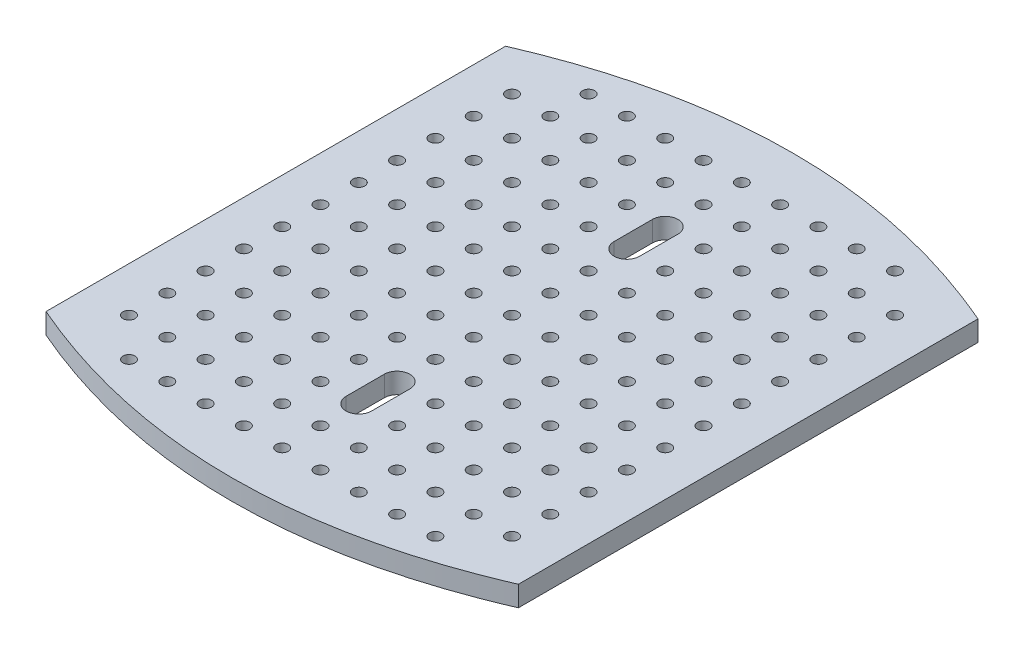
SolidWorks part; units mm, degrees
ref_plane "Front Plane" through (0, 0, 0) normal (0, 0, 1) x (1, 0, 0)
ref_plane "Top Plane" through (0, 0, 0) normal (0, 1, 0) x (1, 0, 0)
ref_plane "Right Plane" through (0, 0, 0) normal (1, 0, 0) x (0, 0, -1)
sketch "Sketch2" plane through (0, 0, 0) normal (0, 1, 0) x (1, 0, 0)
  line L1 (-92.5, 110) -> (92.5, 110)
  line L2 (-92.5, 110) -> (-92.5, -110)
  line L3 (-92.5, -110) -> (92.5, -110)
  line L4 (92.5, 110) -> (92.5, -110)
  line L5 (-92.5, 110) -> (92.5, -110) construction
  line L6 (-92.5, -110) -> (92.5, 110) construction
  point P0 (0, 0)
  dimension "D1" = 220
  dimension "D2" = 185
extrude "Boss-Extrude1" add sketch "Sketch2" along normal blind 8
sketch "Sketch3" plane through (0, 0, 0) normal (0, 1, 0) x (1, 0, 0)
  line L1 (-92.5, 110) -> (-92.5, 90)
  line L3 (-92.5, 110) -> (-92.5, -110) construction
  line L4 (92.5, 110) -> (92.5, 90)
  line L12 (92.5, -110) -> (92.5, 110) construction
  line L13 (92.5, 110) -> (-92.5, 110) construction
  line L14 (92.5, 110) -> (-92.5, 110)
  line L15 (-4.4, 0) -> (4.4, 0) construction
  line L16 (92.5, -110) -> (-92.5, -110)
  line L17 (92.5, -110) -> (92.5, -90)
  line L18 (-92.5, -110) -> (-92.5, -90)
  spline S0 degree 2 poles (-92.5, 90) (0, 130) (92.5, 90) knots 0 0 0 1 1 1
  spline S1 degree 2 poles (-92.5, -90) (0, -130) (92.5, -90) knots 0 0 0 1 1 1
  point P8 (0, 110)
  point P17 (0, -110)
  dimension "D2" = 20
  dimension "D1" = 20
extrude "Cut-Extrude1" cut sketch "Sketch3" against normal blind 8 and the other way through all contours L1 S0 L14 | L14 S0 L4 | S1 L16 L17 | S1 L18 L16 region at (-69.375, 0, -104) region at (69.375, 0, -104) region at (-69.375, 0, 104) region at (69.375, 0, 104)
sketch "Sketch5" plane through (0, 0, 0) normal (0, 1, 0) x (1, 0, 0)
  line L0 (-92.5, -90) -> (92.5, -90) construction
  line L1 (-92.5, 90) -> (92.5, 90) construction
  line L3 (-92.5, 90) -> (-92.5, -90) construction
  circle A0 centre (-75, -90) radius 2.35
  circle A1 centre (-60, -90) radius 2.35
  circle A2 centre (-45, -90) radius 2.35
  circle A3 centre (-30, -90) radius 2.35
  circle A4 centre (-15, -90) radius 2.35
  circle A5 centre (0, -90) radius 2.35
  circle A6 centre (15, -90) radius 2.35
  circle A7 centre (30, -90) radius 2.35
  circle A8 centre (45, -90) radius 2.35
  circle A9 centre (60, -90) radius 2.35
  circle A11 centre (-60, -75) radius 2.35
  circle A12 centre (-45, -75) radius 2.35
  circle A13 centre (-30, -75) radius 2.35
  circle A14 centre (-15, -75) radius 2.35
  circle A15 centre (0, -75) radius 2.35
  circle A16 centre (15, -75) radius 2.35
  circle A17 centre (30, -75) radius 2.35
  circle A18 centre (45, -75) radius 2.35
  circle A19 centre (60, -75) radius 2.35
  circle A20 centre (75, -75) radius 2.35
  circle A21 centre (-60, -60) radius 2.35
  circle A22 centre (-45, -60) radius 2.35
  circle A23 centre (-30, -60) radius 2.35
  circle A24 centre (-15, -60) radius 2.35
  circle A25 centre (0, -60) radius 2.35
  circle A26 centre (15, -60) radius 2.35
  circle A27 centre (30, -60) radius 2.35
  circle A28 centre (45, -60) radius 2.35
  circle A29 centre (60, -60) radius 2.35
  circle A30 centre (75, -60) radius 2.35
  circle A31 centre (-60, -45) radius 2.35
  circle A32 centre (-45, -45) radius 2.35
  circle A33 centre (-30, -45) radius 2.35
  circle A34 centre (-15, -45) radius 2.35
  circle A35 centre (0, -45) radius 2.35
  circle A36 centre (15, -45) radius 2.35
  circle A37 centre (30, -45) radius 2.35
  circle A38 centre (45, -45) radius 2.35
  circle A39 centre (60, -45) radius 2.35
  circle A40 centre (75, -45) radius 2.35
  circle A41 centre (-60, -30) radius 2.35
  circle A42 centre (-45, -30) radius 2.35
  circle A43 centre (-30, -30) radius 2.35
  circle A44 centre (-15, -30) radius 2.35
  circle A45 centre (0, -30) radius 2.35
  circle A46 centre (15, -30) radius 2.35
  circle A47 centre (30, -30) radius 2.35
  circle A48 centre (45, -30) radius 2.35
  circle A49 centre (60, -30) radius 2.35
  circle A50 centre (75, -30) radius 2.35
  circle A51 centre (-60, -15) radius 2.35
  circle A52 centre (-45, -15) radius 2.35
  circle A53 centre (-30, -15) radius 2.35
  circle A54 centre (-15, -15) radius 2.35
  circle A55 centre (0, -15) radius 2.35
  circle A56 centre (15, -15) radius 2.35
  circle A57 centre (30, -15) radius 2.35
  circle A58 centre (45, -15) radius 2.35
  circle A59 centre (60, -15) radius 2.35
  circle A60 centre (75, -15) radius 2.35
  circle A61 centre (-60, 0) radius 2.35
  circle A62 centre (-45, 0) radius 2.35
  circle A63 centre (-30, 0) radius 2.35
  circle A64 centre (-15, 0) radius 2.35
  circle A65 centre (0, 0) radius 2.35
  circle A66 centre (15, 0) radius 2.35
  circle A67 centre (30, 0) radius 2.35
  circle A68 centre (45, 0) radius 2.35
  circle A69 centre (60, 0) radius 2.35
  circle A70 centre (75, 0) radius 2.35
  circle A71 centre (-60, 15) radius 2.35
  circle A72 centre (-45, 15) radius 2.35
  circle A73 centre (-30, 15) radius 2.35
  circle A74 centre (-15, 15) radius 2.35
  circle A75 centre (0, 15) radius 2.35
  circle A76 centre (15, 15) radius 2.35
  circle A77 centre (30, 15) radius 2.35
  circle A78 centre (45, 15) radius 2.35
  circle A79 centre (60, 15) radius 2.35
  circle A80 centre (75, 15) radius 2.35
  circle A81 centre (-60, 30) radius 2.35
  circle A82 centre (-45, 30) radius 2.35
  circle A83 centre (-30, 30) radius 2.35
  circle A84 centre (-15, 30) radius 2.35
  circle A85 centre (0, 30) radius 2.35
  circle A86 centre (15, 30) radius 2.35
  circle A87 centre (30, 30) radius 2.35
  circle A88 centre (45, 30) radius 2.35
  circle A89 centre (60, 30) radius 2.35
  circle A90 centre (75, 30) radius 2.35
  circle A91 centre (-60, 45) radius 2.35
  circle A92 centre (-45, 45) radius 2.35
  circle A93 centre (-30, 45) radius 2.35
  circle A94 centre (-15, 45) radius 2.35
  circle A95 centre (0, 45) radius 2.35
  circle A96 centre (15, 45) radius 2.35
  circle A97 centre (30, 45) radius 2.35
  circle A98 centre (45, 45) radius 2.35
  circle A99 centre (60, 45) radius 2.35
  circle A100 centre (75, 45) radius 2.35
  circle A101 centre (-60, 60) radius 2.35
  circle A102 centre (-45, 60) radius 2.35
  circle A103 centre (-30, 60) radius 2.35
  circle A104 centre (-15, 60) radius 2.35
  circle A105 centre (0, 60) radius 2.35
  circle A106 centre (15, 60) radius 2.35
  circle A107 centre (30, 60) radius 2.35
  circle A108 centre (45, 60) radius 2.35
  circle A109 centre (60, 60) radius 2.35
  circle A110 centre (75, 60) radius 2.35
  circle A111 centre (-60, 75) radius 2.35
  circle A112 centre (-45, 75) radius 2.35
  circle A113 centre (-30, 75) radius 2.35
  circle A114 centre (-15, 75) radius 2.35
  circle A115 centre (0, 75) radius 2.35
  circle A116 centre (15, 75) radius 2.35
  circle A117 centre (30, 75) radius 2.35
  circle A118 centre (45, 75) radius 2.35
  circle A119 centre (60, 75) radius 2.35
  circle A120 centre (75, 75) radius 2.35
  circle A121 centre (-60, 90) radius 2.35
  circle A122 centre (-45, 90) radius 2.35
  circle A123 centre (-30, 90) radius 2.35
  circle A124 centre (-15, 90) radius 2.35
  circle A125 centre (0, 90) radius 2.35
  circle A126 centre (15, 90) radius 2.35
  circle A127 centre (30, 90) radius 2.35
  circle A128 centre (45, 90) radius 2.35
  circle A129 centre (60, 90) radius 2.35
  circle A131 centre (-75, -75) radius 2.35
  circle A132 centre (-75, -60) radius 2.35
  circle A133 centre (-75, -45) radius 2.35
  circle A134 centre (-75, -30) radius 2.35
  circle A135 centre (-75, -15) radius 2.35
  circle A136 centre (-75, 0) radius 2.35
  circle A137 centre (-75, 15) radius 2.35
  circle A138 centre (-75, 30) radius 2.35
  circle A139 centre (-75, 45) radius 2.35
  circle A140 centre (-75, 60) radius 2.35
  circle A141 centre (-75, 75) radius 2.35
  circle A143 centre (-75, 90) radius 2.35 [skipped]
  circle A144 centre (75, 90) radius 2.35 [skipped]
  circle A145 centre (75, -90) radius 2.35 [skipped]
  point P8 (-75, -90)
  point P13 (-60, -90)
  point P14 (-45, -90)
  point P15 (-30, -90)
  point P16 (-15, -90)
  point P17 (0, -90)
  point P18 (15, -90)
  point P19 (30, -90)
  point P20 (45, -90)
  point P21 (60, -90)
  point P22 (75, -90)
  point P23 (-60, -75)
  point P24 (-45, -75)
  point P25 (-30, -75)
  point P26 (-15, -75)
  point P27 (0, -75)
  point P28 (15, -75)
  point P29 (30, -75)
  point P30 (45, -75)
  point P31 (60, -75)
  point P32 (75, -75)
  point P33 (-60, -60)
  point P34 (-45, -60)
  point P35 (-30, -60)
  point P36 (-15, -60)
  point P37 (0, -60)
  point P38 (15, -60)
  point P39 (30, -60)
  point P40 (45, -60)
  point P41 (60, -60)
  point P42 (75, -60)
  point P43 (-60, -45)
  point P44 (-45, -45)
  point P45 (-30, -45)
  point P46 (-15, -45)
  point P47 (0, -45)
  point P48 (15, -45)
  point P49 (30, -45)
  point P50 (45, -45)
  point P51 (60, -45)
  point P52 (75, -45)
  point P53 (-60, -30)
  point P54 (-45, -30)
  point P55 (-30, -30)
  point P56 (-15, -30)
  point P57 (0, -30)
  point P58 (15, -30)
  point P59 (30, -30)
  point P60 (45, -30)
  point P61 (60, -30)
  point P62 (75, -30)
  point P63 (-60, -15)
  point P64 (-45, -15)
  point P65 (-30, -15)
  point P66 (-15, -15)
  point P67 (0, -15)
  point P68 (15, -15)
  point P69 (30, -15)
  point P70 (45, -15)
  point P71 (60, -15)
  point P72 (75, -15)
  point P73 (-60, 0)
  point P74 (-45, 0)
  point P75 (-30, 0)
  point P76 (-15, 0)
  point P77 (0, 0)
  point P78 (15, 0)
  point P79 (30, 0)
  point P80 (45, 0)
  point P81 (60, 0)
  point P82 (75, 0)
  point P83 (-60, 15)
  point P84 (-45, 15)
  point P85 (-30, 15)
  point P86 (-15, 15)
  point P87 (0, 15)
  point P88 (15, 15)
  point P89 (30, 15)
  point P90 (45, 15)
  point P91 (60, 15)
  point P92 (75, 15)
  point P93 (-60, 30)
  point P94 (-45, 30)
  point P95 (-30, 30)
  point P96 (-15, 30)
  point P97 (0, 30)
  point P98 (15, 30)
  point P99 (30, 30)
  point P100 (45, 30)
  point P101 (60, 30)
  point P102 (75, 30)
  point P103 (-60, 45)
  point P104 (-45, 45)
  point P105 (-30, 45)
  point P106 (-15, 45)
  point P107 (0, 45)
  point P108 (15, 45)
  point P109 (30, 45)
  point P110 (45, 45)
  point P111 (60, 45)
  point P112 (75, 45)
  point P113 (-60, 60)
  point P114 (-45, 60)
  point P115 (-30, 60)
  point P116 (-15, 60)
  point P117 (0, 60)
  point P118 (15, 60)
  point P119 (30, 60)
  point P120 (45, 60)
  point P121 (60, 60)
  point P122 (75, 60)
  point P123 (-60, 75)
  point P124 (-45, 75)
  point P125 (-30, 75)
  point P126 (-15, 75)
  point P127 (0, 75)
  point P128 (15, 75)
  point P129 (30, 75)
  point P130 (45, 75)
  point P131 (60, 75)
  point P132 (75, 75)
  point P133 (-60, 90)
  point P134 (-45, 90)
  point P135 (-30, 90)
  point P136 (-15, 90)
  point P137 (0, 90)
  point P138 (15, 90)
  point P139 (30, 90)
  point P140 (45, 90)
  point P141 (60, 90)
  point P142 (75, 90)
  point P143 (-75, -75)
  point P144 (-75, -60)
  point P145 (-75, -45)
  point P146 (-75, -30)
  point P147 (-75, -15)
  point P148 (-75, 0)
  point P149 (-75, 15)
  point P150 (-75, 30)
  point P151 (-75, 45)
  point P152 (-75, 60)
  point P153 (-75, 75)
  point P154 (-75, 90)
  dimension "D7" = 4.7
  dimension "D1" = 17.5
  dimension "D2" = 11
  dimension "D5" = 15
  dimension "D6" = 17.5
  dimension "D8" = 11
  dimension "D9" = 13
  dimension "D4" = 15
  dimension "D3" = 13
extrude "Cut-Extrude4" cut sketch "Sketch5" along normal blind 8
sketch "Sketch8" plane through (0, 0, 0) normal (0, 1, 0) x (1, 0, 0)
  line L0 (0, 60) -> (0, 45) construction
  line L1 (5, 60) -> (5, 45)
  line L2 (-5, 60) -> (-5, 45)
  line L3 (-4.4, 0) -> (4.4, 0) construction
  line L4 (0, -60) -> (0, -45) construction
  line L5 (5, -60) -> (5, -45)
  line L6 (-5, -60) -> (-5, -45)
  arc A0 (5, 60) -> (-5, 60) centre (0, 60) ccw
  arc A1 (-5, 45) -> (5, 45) centre (0, 45) ccw
  arc A2 (5, -60) -> (-5, -60) centre (0, -60) cw
  arc A3 (-5, -45) -> (5, -45) centre (0, -45) cw
  point P4 (0, 52.5)
  point P13 (0, -52.5)
  dimension "D1" = 10
extrude "Cut-Extrude6" cut sketch "Sketch8" along normal blind 8
sketch "Sketch10" plane through (0, 0, 0) normal (0, 1, 0) x (1, 0, 0)
  circle A0 centre (-75, -90) radius 2.35
  dimension "D1" = 4.7
extrude "Boss-Extrude2" add sketch "Sketch10" along normal up to surface (8 mm away) separate body up to face at (0, 8, 52.5)
combine bodies "Combine1" operation type add bodies to combine 105 104
